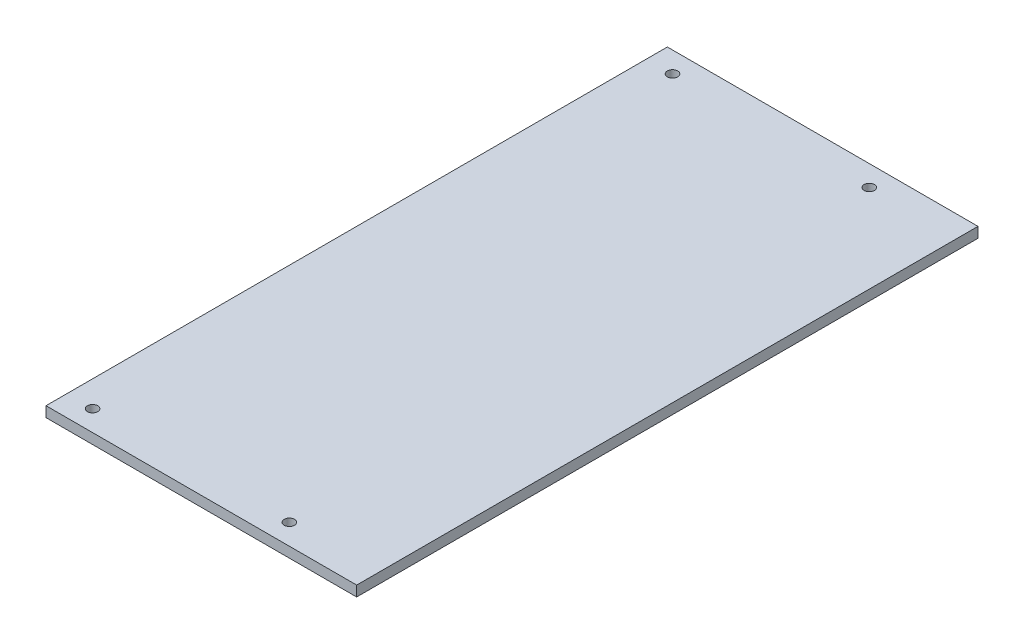
SolidWorks part; units mm, degrees
ref_plane "Front Plane" through (0, 0, 0) normal (0, 0, 1) x (1, 0, 0)
ref_plane "Top Plane" through (0, 0, 0) normal (0, 1, 0) x (1, 0, 0)
ref_plane "Right Plane" through (0, 0, 0) normal (1, 0, 0) x (0, 0, -1)
sketch "Sketch1" plane through (0, 0, 0) normal (0, 1, 0) x (1, 0, 0)
  line L0 (-37.5, 84) -> (-37.5, -84) construction
  line L1 (-45, -90) -> (45, -90)
  line L2 (-45, -90) -> (-45, 90)
  line L3 (-45, 90) -> (45, 90)
  line L4 (45, -90) -> (45, 90)
  line L5 (-45, -90) -> (45, 90) construction
  line L6 (-45, 90) -> (45, -90) construction
  line L7 (-37.5, -84) -> (19.5, -84) construction
  line L8 (19.5, -84) -> (19.5, 84) construction
  line L9 (19.5, 84) -> (-37.5, 84) construction
  circle A4 centre (19.5, -84) radius 1.5
  circle A5 centre (-37.5, -84) radius 1.5
  circle A6 centre (19.5, 84) radius 1.5
  circle A7 centre (-37.5, 84) radius 1.5
  point P0 (0, 0)
  dimension "D3" = 3
  dimension "D4" = 6
  dimension "D5" = 7.5
  dimension "D6" = 57
  dimension "D7" = 168
  dimension "D1" = 90
  dimension "D2" = 180
extrude "Boss-Extrude1" add sketch "Sketch1" along normal blind 3
